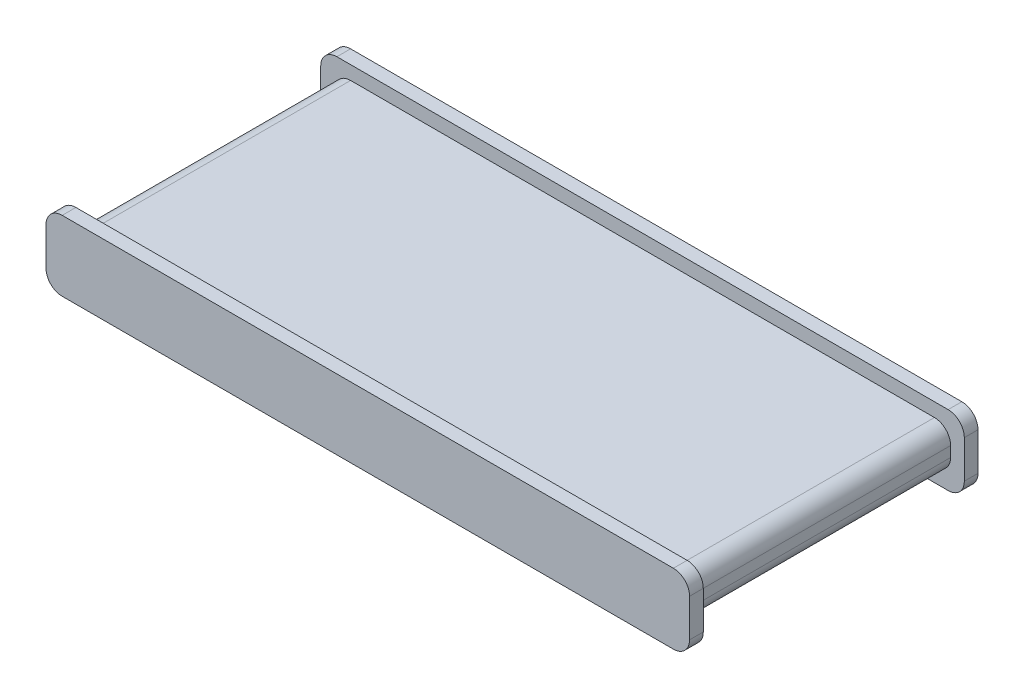
SolidWorks part; units mm, degrees
material "ABS"
ref_plane "X-Y Datum" through (0, 0, 0) normal (0, 0, 1) x (1, 0, 0)
ref_plane "X-Z Datum" through (0, 0, 0) normal (0, 1, 0) x (1, 0, 0)
ref_plane "Y-Z Datum" through (0, 0, 0) normal (1, 0, 0) x (0, 0, -1)
sketch "Sketch2" plane through (0, 0, 0) normal (0, 0, 1) x (1, 0, 0)
  line L6 (114.3, 7.9241) -> (0, 7.9241)
  line L7 (114.3, 7.9241) -> (114.3, 0)
  line L8 (114.3, 0) -> (0, 0)
  line L9 (0, 7.9241) -> (0, 0)
  dimension "D1" = 114.3
extrude "Boss-Extrude1" add sketch "Sketch2" along normal blind 48.42
fillet "Fillet1" radius 3 4 edges at (114.3, 7.9241, 24.21) (114.3, 0, 24.21) (0, 7.9241, 24.21) (0, 0, 24.21)
sketch "Sketch3" plane through (0, 0, 48.42) normal (0, 0, 1) x (1, 0, 0)
  line L0 (111.3, 7.9241) -> (3, 7.9241) construction
  line L1 (-2.54, -2.54) -> (116.84, -2.54)
  line L2 (-2.54, -2.54) -> (-2.54, 10.4641)
  line L3 (-2.54, 10.4641) -> (116.84, 10.4641)
  line L4 (116.84, -2.54) -> (116.84, 10.4641)
  line L5 (3, 0) -> (111.3, 0) construction
  line L6 (0, 4.9241) -> (0, 3) construction
  line L7 (114.3, 3) -> (114.3, 4.9241) construction
  dimension "D1" = 2.54
  dimension "D2" = 2.54
  dimension "D3" = 2.54
  dimension "D4" = 2.54
extrude "Boss-Extrude2" add sketch "Sketch3" along normal blind 2.54
sketch "Sketch4" plane through (0, 0, 0) normal (0, 0, -1) x (-1, 0, 0)
  line L1 (-116.84, 10.4641) -> (2.54, 10.4641)
  line L2 (-116.84, 10.4641) -> (-116.84, -2.54)
  line L3 (-116.84, -2.54) -> (2.54, -2.54)
  line L4 (2.54, 10.4641) -> (2.54, -2.54)
extrude "Boss-Extrude3" add sketch "Sketch4" along normal blind 2.54
fillet "Fillet2" radius 3 8 edges at (-2.54, -2.54, -1.27) (-2.54, 10.4641, -1.27) (116.84, 10.4641, -1.27) (116.84, -2.54, -1.27) (116.84, 10.4641, 49.69) (116.84, -2.54, 49.69) (-2.54, 10.4641, 49.69) (-2.54, -2.54, 49.69)
